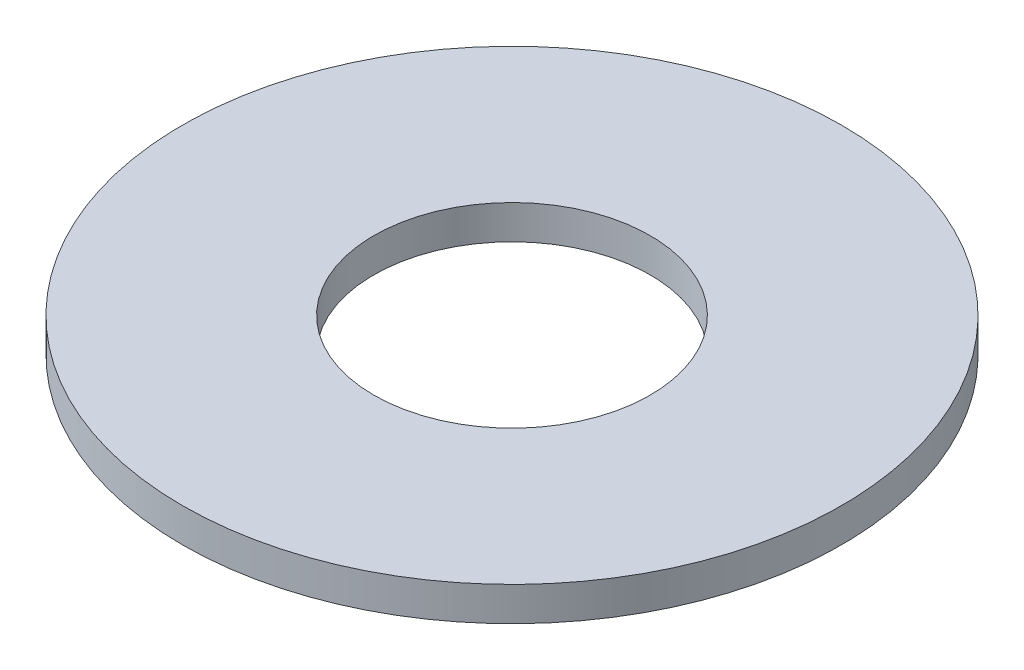
SolidWorks part; units mm, degrees
ref_plane "Front Plane" through (0, 0, 0) normal (0, 0, 1) x (1, 0, 0)
ref_plane "Top Plane" through (0, 0, 0) normal (0, 1, 0) x (1, 0, 0)
ref_plane "Right Plane" through (0, 0, 0) normal (1, 0, 0) x (0, 0, -1)
sketch "Sketch1" plane through (0, 0, 0) normal (0, 1, 0) x (1, 0, 0)
  circle A0 centre (0, 0) radius 77.5
  dimension "FLANGE_OD" = 155
extrude "Boss-Extrude1" add sketch "Sketch1" along normal blind 8
sketch "Sketch2" plane through (0, 0, 0) normal (0, 1, 0) x (1, 0, 0)
  circle A0 centre (0, 0) radius 32.5
  dimension "BORE_D" = 65
extrude "Cut-Extrude1" cut sketch "Sketch2" along normal through all
sketch "Sketch3" plane through (0, 8, 0) normal (0, 1, 0) x (1, 0, 0)
  circle A0 centre (0, 0) radius 26.6639 construction
  circle A1 centre (-26.6639, 0) radius 5.1384
  dimension "BOLT_D" = 10.2767
  dimension "BOLT_PCD" = 53.3278
extrude "Cut-Extrude2" cut sketch "Sketch3" against normal blind 7.0511 rebuild error yes
pattern_circular "CirPattern1" count 4 over 360 rebuild error yes
